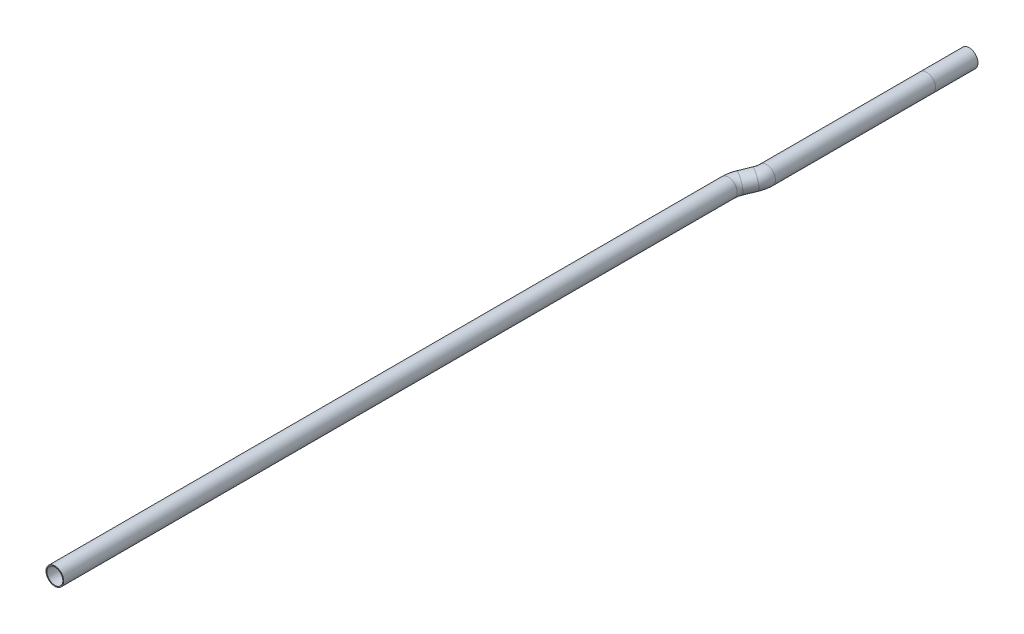
SolidWorks part; units mm, degrees
material "6061 Alloy"
ref_plane "Front Plane" through (0, 0, 0) normal (0, 0, 1) x (1, 0, 0)
ref_plane "Top Plane" through (0, 0, 0) normal (0, 1, 0) x (1, 0, 0)
ref_plane "Right Plane" through (0, 0, 0) normal (1, 0, 0) x (0, 0, -1)
sketch "Sketch1" plane through (0, 0, 0) normal (0, 0, 1) x (1, 0, 0)
  line L0 (0, 0) -> (3.7368, 0.7433) construction
  circle A0 centre (3.7368, 0.7433) radius 2.8575
  circle A1 centre (3.7368, 0.7433) radius 3.175
  dimension "D1" = 6.35
  dimension "D2" = 0.3175
ref_axis "Axis1" through (3.7368, 0.7433, -7.8366) along (0, 0, 1)
ref_plane "Plane1" through (0, 0, 0) normal (-0.1951, 0.9808, 0) x (0, 0, 1)
sketch "Sketch2" plane through (0, 0, 0) normal (-0.1951, 0.9808, 0) x (0, 0, 1)
  line L0 (0, 0) -> (0, 3.81) construction
  line L1 (0, 3.81) -> (-12.7, 3.81)
  line L2 (0, 3.81) -> (2.54, 3.81)
  line L3 (7.0301, 5.6699) -> (12.2004, 10.8401) construction
  line L4 (16.6905, 12.7) -> (51.8895, 12.7) construction
  line L5 (56.3796, 10.8401) -> (65.3599, 1.8599) construction
  line L6 (69.85, 0) -> (311.15, 0)
  line L8 (0, 0) -> (36.3164, 0) construction
  line L9 (290.83, 3.175) -> (290.83, -3.175) construction
  line L10 (76.2, 3.175) -> (76.2, -3.175) construction
  line L11 (0, 0.635) -> (0, 6.985) construction
  line L12 (2.54, 3.81) -> (59.8479, 3.81)
  line L13 (63.0229, 2.9593) -> (66.675, 0.8507)
  arc A0 (2.54, 3.81) -> (7.0301, 5.6699) centre (2.54, 10.16) ccw construction
  arc A1 (12.2004, 10.8401) -> (16.6905, 12.7) centre (16.6905, 6.35) cw construction
  arc A2 (51.8895, 12.7) -> (56.3796, 10.8401) centre (51.8895, 6.35) cw construction
  arc A3 (65.3599, 1.8599) -> (69.85, 0) centre (69.85, 6.35) ccw construction
  arc A4 (59.8479, 3.81) -> (63.0229, 2.9593) centre (59.8479, -2.54) cw
  arc A5 (66.675, 0.8507) -> (69.85, 0) centre (69.85, 6.35) ccw
  point P30 (59.3755, 3.81)
  point P31 (60.1143, 3.81)
  dimension "D3" = 6.35
  dimension "D4" = 6.35
  dimension "D5" = 6.35
  dimension "D6" = 6.35
  dimension "D13" = 6.35
  dimension "D14" = 6.35
  dimension "D1" = 3.81
  dimension "D2" = 12.7
  dimension "D7" = 20.32
  dimension "D8" = 12.7
  dimension "D9" = 135
  dimension "D10" = 135
  dimension "D11" = 6.35
  dimension "D12" = 2.54
  dimension "D15" = 30
sweep "Sweep1" add profiles "Sketch1" path "Sketch2"
